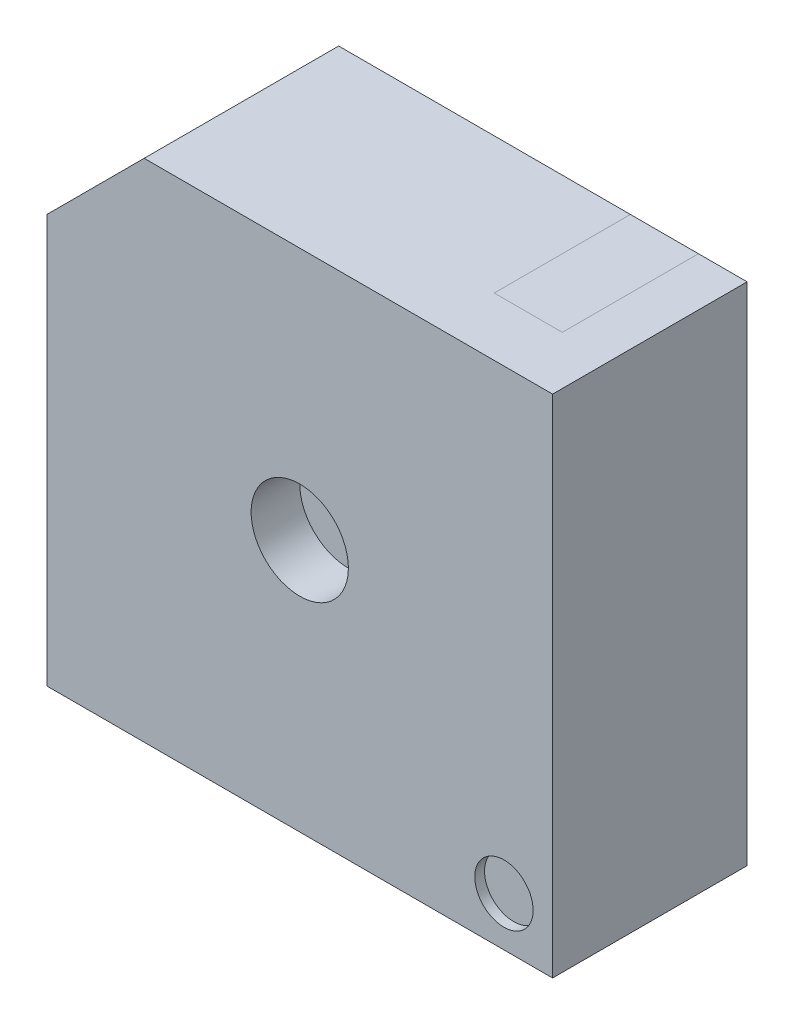
SolidWorks part; units mm, degrees
ref_plane "前视基准面" through (0, 0, 0) normal (0, 0, 1) x (1, 0, 0)
ref_plane "上视基准面" through (0, 0, 0) normal (0, 1, 0) x (1, 0, 0)
ref_plane "右视基准面" through (0, 0, 0) normal (1, 0, 0) x (0, 0, -1)
sketch "草图1" plane through (0, 0, 0) normal (0, 0, 1) x (1, 0, 0)
  line L0 (-4.2874, 0) -> (5.8198, 0) construction
  line L1 (-1.6, 2.6) -> (2.6, 2.6)
  line L2 (-2.6, 1.6) -> (-2.6, -2.6)
  line L3 (-2.6, -2.6) -> (2.6, -2.6)
  line L4 (2.6, 2.6) -> (2.6, -2.6)
  line L5 (0, 6.3088) -> (0, -4.5203) construction
  line L6 (0, -4.5203) -> (0, -3.9553) construction
  line L7 (-2.6, 1.6) -> (-1.6, 2.6)
  dimension "D1" = 5.2
  dimension "D2" = 5.2
  dimension "D3" = 1
  dimension "D4" = 135
extrude "凸台-拉伸1" add sketch "草图1" along normal blind 2
sketch "草图2" plane through (0, 0, 2) normal (0, 0, 1) x (1, 0, 0)
  line L0 (2.6, -2.6) -> (2.6, 2.6) construction
  line L1 (-2.6, -2.6) -> (2.6, -2.6) construction
  circle A0 centre (0, 0) radius 0.5
  circle A1 centre (2.1, -2.098) radius 0.3
  dimension "D1" = 1
  dimension "D4" = 0.6
  dimension "D2" = 0.5
  dimension "D3" = 0.502
extrude "切除-拉伸1" cut sketch "草图2" against normal blind 0.5 contours A0 region at (0, 0, 2)
extrude "切除-拉伸2" cut sketch "草图2<3>" against normal blind 0.1 contours A1 region at (2.1, -2.098, 2)
sketch "草图2<3>" plane through (0, 0, 2) normal (0, 0, 1) x (1, 0, 0) same geometry as "草图2"
sketch3d "3D草图1"
  line L0 (-2.1, -2.6, 0) -> (-2.1, -2.6, 1.4)
  line L1 (-2.6, -2.6, 0) -> (2.6, -2.6, 0) construction
  line L2 (-2.1, -2.6, 1.4) -> (-1.4, -2.6, 1.4)
  line L3 (-1.4, -2.6, 1.4) -> (-1.4, -2.6, 0)
  line L4 (1.4, -2.6, 0) -> (1.4, -2.6, 1.4)
  line L5 (1.4, -2.6, 1.4) -> (2.1, -2.6, 1.4)
  line L6 (2.1, -2.6, 1.4) -> (2.1, -2.6, 0)
  line L7 (-2.1, -2.6, 0) -> (-2.1, -1.7, 0)
  line L8 (-2.1, -1.7, 0) -> (-1.4, -1.7, 0)
  line L9 (-1.4, -1.7, 0) -> (-1.4, -2.6, 0)
  line L10 (1.4, -2.6, 0) -> (1.4, -1.7, 0)
  line L11 (1.4, -1.7, 0) -> (2.1, -1.7, 0)
  line L12 (2.1, -1.7, 0) -> (2.1, -2.6, 0)
  line L13 (0, 0, 0) -> (0, -6.5888, 0) construction
  line L14 (1.4, 2.6, 0) -> (1.4, 1.7, 0)
  line L15 (2.6, 2.6, 0) -> (-1.6, 2.6, 0) construction
  line L16 (1.4, 1.7, 0) -> (2.1, 1.7, 0)
  line L17 (2.1, 1.7, 0) -> (2.1, 2.6, 0)
  line L18 (1.4, 2.6, 0) -> (1.4, 2.6, 0.7938)
  line L19 (1.4, 2.6, 0.7938) -> (2.1, 2.6, 0.7938)
  line L20 (2.1, 2.6, 0.7938) -> (2.1, 2.6, 0)
  dimension "D1" = 1.4
  dimension "D2" = 0.7
  dimension "D3" = 0.9
  dimension "D4" = 2.8
  dimension "D5" = 1.4
sketch "草图3" plane through (0, 0, 0) normal (0, 0, -1) x (-1, 0, 0)
  line L1 (-2.1, -1.7) -> (-1.4, -1.7)
  line L2 (-2.1, -1.7) -> (-2.1, -2.6)
  line L3 (-2.1, -2.6) -> (-1.4, -2.6)
  line L4 (-1.4, -1.7) -> (-1.4, -2.6)
  line L5 (1.4, -2.6) -> (2.1, -2.6)
  line L6 (1.4, -2.6) -> (1.4, -1.7)
  line L7 (1.4, -1.7) -> (2.1, -1.7)
  line L8 (2.1, -2.6) -> (2.1, -1.7)
  line L9 (-2.1, 2.6) -> (-1.4, 2.6)
  line L10 (-2.1, 2.6) -> (-2.1, 1.7)
  line L11 (-2.1, 1.7) -> (-1.4, 1.7)
  line L12 (-1.4, 2.6) -> (-1.4, 1.7)
split line "分割线3"
sketch "草图4" plane through (0, 2.6, 0) normal (0, 1, 0) x (1, 0, 0)
  line L0 (1.4, -1.4) -> (2.1, -1.4)
  line L1 (1.4, 0) -> (2.1, 0)
  line L2 (1.4, 0) -> (1.4, -1.4)
  line L4 (2.1, 0) -> (2.1, -1.4)
  line L5 (2.1, -0.7938) -> (2.1, 0) construction
  line L6 (1.4, -1.4) -> (2.1, -1.4) construction
sketch "草图5" plane through (0, -2.6, 0) normal (0, -1, 0) x (1, 0, 0)
  line L0 (-1.4, 1.4) -> (-1.4, 0) construction
  line L1 (-2.1, 1.4) -> (-1.4, 1.4)
  line L2 (-2.1, 1.4) -> (-2.1, 0)
  line L3 (-2.1, 0) -> (-1.4, 0)
  line L4 (-1.4, 1.4) -> (-1.4, 0)
  line L5 (-1.4, 0) -> (1.4, 0) construction
  line L7 (1.4, 1.4) -> (2.1, 1.4)
  line L8 (1.4, 1.4) -> (1.4, 0)
  line L9 (1.4, 0) -> (2.1, 0)
  line L10 (2.1, 1.4) -> (2.1, 0)
split line "分割线4"
split line "分割线5"
